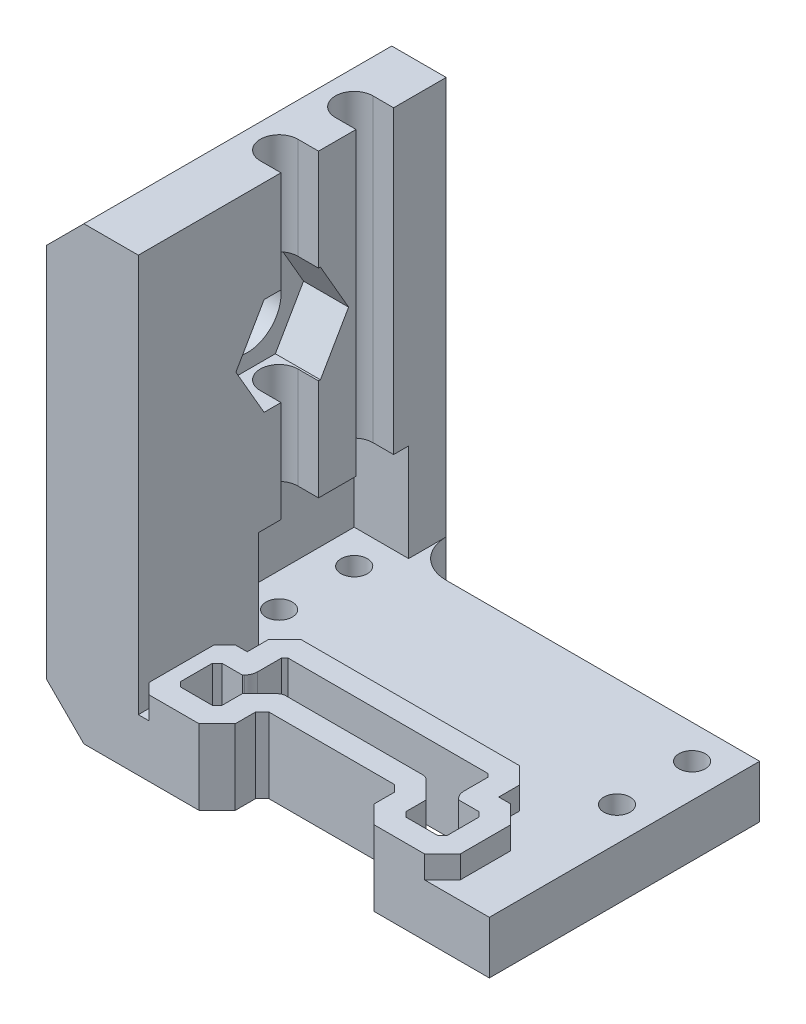
SolidWorks part; units mm, degrees
ref_plane "Front Plane" through (0, 0, 0) normal (0, 0, 1) x (1, 0, 0)
ref_plane "Top Plane" through (0, 0, 0) normal (0, 1, 0) x (1, 0, 0)
ref_plane "Right Plane" through (0, 0, 0) normal (1, 0, 0) x (0, 0, -1)
ref_plane "Plane1" through (0, 200, 0) normal (0, 1, 0) x (1, 0, 0)
sketch "Sketch1" plane through (0, 200, 0) normal (0, 1, 0) x (1, 0, 0)
  line L0 (0, -3.8557) -> (0.25, -4)
  line L1 (0.25, -4) -> (9.0787, -4)
  line L2 (10.1394, -4.4394) -> (12.5, -6.8)
  line L3 (12.5, -6.8) -> (12.5, -9.5)
  line L4 (12.5, -9.5) -> (13, -10)
  line L5 (13, -10) -> (17, -10)
  line L6 (17, -10) -> (17.5, -9.5)
  line L7 (17.5, -9.5) -> (17.5, -5.5)
  line L8 (17.5, -5.5) -> (17, -5)
  line L9 (17, -5) -> (14.3, -5)
  line L10 (14.3, -5) -> (14.0858, -4.7858)
  line L11 (13.5, -3.3716) -> (13.5, -0.3)
  line L12 (13.5, -0.3) -> (13.2, 0)
  line L13 (13.2, 0) -> (7.5, 0)
  line L14 (7.5, 0) -> (7.4, -0.1)
  line L15 (7.4, -0.1) -> (-7.4, -0.1)
  line L16 (-7.4, -0.1) -> (-7.5, 0)
  line L17 (-7.5, 0) -> (-13.2, 0)
  line L18 (-13.2, 0) -> (-13.5, -0.3)
  line L19 (-13.5, -0.3) -> (-13.5, -3.3716)
  line L20 (-14.0858, -4.7858) -> (-14.3, -5)
  line L21 (-14.3, -5) -> (-17, -5)
  line L22 (-17, -5) -> (-17.5, -5.5)
  line L23 (-17.5, -5.5) -> (-17.5, -9.5)
  line L24 (-17.5, -9.5) -> (-17, -10)
  line L25 (-17, -10) -> (-13, -10)
  line L26 (-13, -10) -> (-12.5, -9.5)
  line L27 (-12.5, -9.5) -> (-12.5, -6.8)
  line L28 (-12.5, -6.8) -> (-10.1394, -4.4394)
  line L29 (-9.0787, -4) -> (-0.25, -4)
  line L30 (-0.25, -4) -> (0, -3.8557)
  arc A0 (9.0787, -4) -> (10.1394, -4.4394) centre (9.0787, -5.5) cw
  arc A1 (14.0858, -4.7858) -> (13.5, -3.3716) centre (15.5, -3.3716) cw
  arc A2 (-13.5, -3.3716) -> (-14.0858, -4.7858) centre (-15.5, -3.3716) cw
  arc A3 (-10.1394, -4.4394) -> (-9.0787, -4) centre (-9.0787, -5.5) cw
extrude "Boss-Extrude1" add sketch "Sketch1" against normal blind 400
ref_plane "Plane2" through (0, 210, 0) normal (0, 1, 0) x (1, 0, 0)
sketch "Sketch2" plane through (0, 210, 0) normal (0, 1, 0) x (1, 0, 0)
  line L0 (-8.3538, -7.25) -> (8.3538, -7.25)
  line L1 (8.3538, -7.25) -> (9.25, -8.1462)
  line L2 (13.3036, 0.25) -> (-13.3036, 0.25)
  line L3 (-13.3036, 0.25) -> (-13.75, -0.1965)
  line L4 (-13.75, -0.1965) -> (-13.75, -3.3716)
  line L5 (-14.2626, -4.609) -> (-14.4036, -4.75)
  line L6 (-14.4036, -4.75) -> (-17.1036, -4.75)
  line L7 (-17.1036, -4.75) -> (-17.75, -5.3965)
  line L8 (-17.75, -5.3965) -> (-17.75, -9.6036)
  line L9 (-17.75, -9.6036) -> (-17.1036, -10.25)
  line L10 (-17.1036, -10.25) -> (-12.8965, -10.25)
  line L11 (-12.8965, -10.25) -> (-12.25, -9.6036)
  line L12 (-12.25, -9.6036) -> (-12.25, -6.9036)
  line L13 (-12.25, -6.9036) -> (-9.9626, -4.6162)
  line L14 (-9.0787, -4.25) -> (9.0787, -4.25)
  line L15 (9.9626, -4.6162) -> (12.25, -6.9036)
  line L16 (12.25, -6.9036) -> (12.25, -9.6036)
  line L17 (12.25, -9.6036) -> (12.8965, -10.25)
  line L18 (12.8965, -10.25) -> (17.1036, -10.25)
  line L19 (17.1036, -10.25) -> (17.75, -9.6036)
  line L20 (17.75, -9.6036) -> (17.75, -5.3965)
  line L21 (17.75, -5.3965) -> (17.1036, -4.75)
  line L22 (17.1036, -4.75) -> (14.4036, -4.75)
  line L23 (14.4036, -4.75) -> (14.2626, -4.609)
  line L24 (13.75, -3.3716) -> (13.75, -0.1965)
  line L25 (13.75, -0.1965) -> (13.3036, 0.25)
  line L26 (9.25, -8.1462) -> (9.25, -10.8462)
  line L27 (9.25, -10.8462) -> (11.6538, -13.25)
  line L28 (11.6538, -13.25) -> (18.3462, -13.25)
  line L29 (18.3462, -13.25) -> (20.75, -10.8462)
  line L30 (20.75, -10.8462) -> (20.75, -4.1538)
  line L31 (20.75, -4.1538) -> (18.3462, -1.75)
  line L32 (18.3462, -1.75) -> (16.75, -1.75)
  line L33 (16.75, -1.75) -> (16.75, -1.75)
  line L34 (16.75, -1.75) -> (16.75, 1.0462)
  line L35 (16.75, 1.0462) -> (14.5462, 3.25)
  line L36 (14.5462, 3.25) -> (-14.5462, 3.25)
  line L37 (-14.5462, 3.25) -> (-16.75, 1.0462)
  line L38 (-16.75, 1.0462) -> (-16.75, -1.75)
  line L39 (-16.75, -1.75) -> (-16.75, -1.75)
  line L40 (-16.75, -1.75) -> (-18.3462, -1.75)
  line L41 (-18.3462, -1.75) -> (-20.75, -4.1538)
  line L42 (-20.75, -4.1538) -> (-20.75, -10.8462)
  line L43 (-20.75, -10.8462) -> (-18.3462, -13.25)
  line L44 (-18.3462, -13.25) -> (-11.6538, -13.25)
  line L45 (-11.6538, -13.25) -> (-9.25, -10.8462)
  line L46 (-9.25, -10.8462) -> (-9.25, -8.1462)
  line L47 (-9.25, -8.1462) -> (-8.3538, -7.25)
  arc A0 (-14.2626, -4.609) -> (-13.75, -3.3716) centre (-15.5, -3.3716) ccw
  arc A1 (-9.0787, -4.25) -> (-9.9626, -4.6162) centre (-9.0787, -5.5) ccw
  arc A2 (9.9626, -4.6162) -> (9.0787, -4.25) centre (9.0787, -5.5) ccw
  arc A3 (13.75, -3.3716) -> (14.2626, -4.609) centre (15.5, -3.3716) ccw
  arc A4 (8.3538, -7.25) -> (8.3538, -7.25) centre (8.3538, -7.25) ccw
  arc A5 (16.75, -1.75) -> (16.75, -1.75) centre (16.75, -1.75) ccw
  arc A6 (-16.75, -1.75) -> (-16.75, -1.75) centre (-16.75, -1.75) ccw
  arc A7 (-8.3538, -7.25) -> (-8.3538, -7.25) centre (-8.3538, -7.25) ccw
  dimension "D1" = 3
extrude "Boss-Extrude2" add sketch "Sketch2" along normal blind 10 separate body
sketch "Sketch3" plane through (0, 200, 0) normal (0, 1, 0) x (1, 0, 0)
  line L0 (7.4, -0.1) -> (-7.4, -0.1) construction
  circle A0 centre (0, -0.1) radius 43.001
extrude "Cut-Extrude1" cut sketch "Sketch3" against normal blind 447.3602
sketch "Sketch4" plane through (0, 210, 0) normal (0, -1, 0) x (-1, 0, 0)
  line L0 (-13.3036, 0.25) -> (13.3036, 0.25) construction
  line L1 (27, 22.75) -> (-27, 22.75)
  line L2 (27, 22.75) -> (27, -13.25)
  line L3 (27, -13.25) -> (18.3462, -13.25)
  line L4 (-27, 22.75) -> (-27, -13.25)
  line L5 (-27, -13.25) -> (-18.3462, -13.25)
  line L25 (8.3538, -7.25) -> (9.25, -8.1462)
  line L26 (9.25, -8.1462) -> (9.25, -10.8462)
  line L27 (9.25, -10.8462) -> (11.6538, -13.25)
  line L28 (11.6538, -13.25) -> (18.3462, -13.25)
  line L29 (18.3462, -13.25) -> (20.75, -10.8462)
  line L30 (20.75, -10.8462) -> (20.75, -4.1538)
  line L31 (20.75, -4.1538) -> (18.3462, -1.75)
  line L32 (18.3462, -1.75) -> (16.75, -1.75)
  line L33 (16.75, -1.75) -> (16.75, 1.0462)
  line L34 (16.75, 1.0462) -> (14.5462, 3.25)
  line L35 (14.5462, 3.25) -> (-14.5462, 3.25)
  line L36 (-14.5462, 3.25) -> (-16.75, 1.0462)
  line L37 (-16.75, 1.0462) -> (-16.75, -1.75)
  line L38 (-16.75, -1.75) -> (-18.3462, -1.75)
  line L39 (-18.3462, -1.75) -> (-20.75, -4.1538)
  line L40 (-20.75, -4.1538) -> (-20.75, -10.8462)
  line L41 (-20.75, -10.8462) -> (-18.3462, -13.25)
  line L42 (-18.3462, -13.25) -> (-11.6538, -13.25)
  line L43 (-11.6538, -13.25) -> (-9.25, -10.8462)
  line L44 (-9.25, -10.8462) -> (-9.25, -8.1462)
  line L45 (-9.25, -8.1462) -> (-8.3538, -7.25)
  line L46 (-8.3538, -7.25) -> (8.3538, -7.25)
  line L47 (8.3538, -7.25) -> (9.25, -8.1462)
  line L48 (9.25, -8.1462) -> (9.25, -10.8462)
  line L49 (9.25, -10.8462) -> (11.6538, -13.25)
  line L50 (11.6538, -13.25) -> (18.3462, -13.25)
  line L51 (18.3462, -13.25) -> (20.75, -10.8462)
  line L52 (20.75, -10.8462) -> (20.75, -4.1538)
  line L53 (20.75, -4.1538) -> (18.3462, -1.75)
  line L54 (18.3462, -1.75) -> (16.75, -1.75)
  line L55 (16.75, -1.75) -> (16.75, 1.0462)
  line L56 (16.75, 1.0462) -> (14.5462, 3.25)
  line L57 (14.5462, 3.25) -> (-14.5462, 3.25)
  line L58 (-14.5462, 3.25) -> (-16.75, 1.0462)
  line L59 (-16.75, 1.0462) -> (-16.75, -1.75)
  line L60 (-16.75, -1.75) -> (-18.3462, -1.75)
  line L61 (-18.3462, -1.75) -> (-20.75, -4.1538)
  line L62 (-20.75, -4.1538) -> (-20.75, -10.8462)
  line L63 (-20.75, -10.8462) -> (-18.3462, -13.25)
  line L64 (-18.3462, -13.25) -> (-11.6538, -13.25)
  line L65 (-11.6538, -13.25) -> (-9.25, -10.8462)
  line L66 (-9.25, -10.8462) -> (-9.25, -8.1462)
  line L67 (-9.25, -8.1462) -> (-8.3538, -7.25)
  line L68 (-8.3538, -7.25) -> (8.3538, -7.25)
  point P8 (0, 22.75)
  point P29 (0, 0.25)
  dimension "D2" = 19.5
  dimension "D3" = 54
  dimension "D4" = 0
  dimension "D1" = 0
extrude "Boss-Extrude3" add sketch "Sketch4" against normal blind 7
sketch "Sketch5" plane through (0, 210, 0) normal (0, -1, 0) x (-1, 0, 0)
  line L0 (0, 22.75) -> (0, 9.6848) construction
  line L1 (27, 22.75) -> (-27, 22.75) construction
  line L2 (27, 22.75) -> (27, -13.25) construction
  circle A0 centre (22.5, 18.25) radius 1.75
  circle A1 centre (22.5, 8.25) radius 1.75
  circle A2 centre (-22.5, 8.25) radius 1.75
  circle A3 centre (-22.5, 18.25) radius 1.75
  dimension "D4" = 3.5
  dimension "D1" = 10
  dimension "D2" = 4.5
  dimension "D3" = 4.5
extrude "Cut-Extrude2" cut sketch "Sketch5" against normal blind 33
sketch "Sketch6" plane through (-27, 0, 0) normal (-1, 0, 0) x (0, 0, 1)
  line L1 (-22.75, 210) -> (13.25, 210)
  line L2 (-22.75, 210) -> (-22.75, 270)
  line L3 (-22.75, 270) -> (13.25, 270)
  line L4 (13.25, 210) -> (13.25, 270)
  dimension "D1" = 60
extrude "Boss-Extrude4" add sketch "Sketch6" along normal blind 5
sketch "Sketch7" plane through (0, 217, 0) normal (0, 1, 0) x (1, 0, 0)
  line L0 (-20.75, -10.8462) -> (-20.75, -4.1538) construction
  line L1 (-27, -13.25) -> (-19.75, -13.25)
  line L2 (-27, -13.25) -> (-27, 2.75)
  line L3 (-27, 2.75) -> (-19.75, 2.75)
  line L4 (-19.75, -13.25) -> (-19.75, 2.75)
  dimension "D1" = 1
  dimension "D2" = 16
extrude "Boss-Extrude5" add sketch "Sketch7" along normal up to surface (53 mm away) up to face at (-29.5, 270, -4.75)
sketch "Sketch8" plane through (0, 0, -22.75) normal (0, 0, -1) x (-1, 0, 0)
  line L0 (32, 210) -> (-27, 210) construction
  line L1 (32, 270) -> (19.75, 270)
  line L2 (32, 270) -> (32, 210)
  line L3 (32, 210) -> (19.75, 210)
  line L4 (19.75, 270) -> (19.75, 210)
  dimension "D1" = 0
extrude "Boss-Extrude6" add sketch "Sketch8" along normal blind 5
fillet "Fillet1" radius 5 1 edges at (-19.75, 213.5, -22.75)
sketch "Sketch10" plane through (-27, 0, 0) normal (1, 0, 0) x (0, 0, -1)
  line L0 (22.75, 270) -> (22.75, 217) construction
  line L1 (2.75, 270) -> (22.75, 270)
  line L2 (2.75, 270) -> (2.75, 230)
  line L3 (2.75, 230) -> (22.75, 230)
  line L4 (22.75, 270) -> (22.75, 230)
  dimension "D1" = 40
extrude "Boss-Extrude7" add sketch "Sketch10" along normal up to surface (7.25 mm away) up to face at (-19.75, 231, 6.375)
sketch "Sketch9" plane through (-19.75, 0, 0) normal (1, 0, 0) x (0, 0, -1)
  line L0 (-13.25, 250) -> (27.75, 250) construction
  line L1 (14.7555, 250) -> (11.0027, 256.5)
  line L2 (11.0027, 256.5) -> (3.4972, 256.5)
  line L3 (3.4972, 256.5) -> (-0.2556, 250)
  line L4 (-0.2556, 250) -> (3.4972, 243.5)
  line L5 (3.4972, 243.5) -> (11.0027, 243.5)
  line L6 (11.0027, 243.5) -> (14.7555, 250)
  line L8 (-13.25, 270) -> (-13.25, 217) construction
  line L9 (27.75, 270) -> (27.75, 217) construction
  line L10 (27.75, 270) -> (-13.25, 270) construction
  circle A0 centre (7.25, 250) radius 6.5 construction
  dimension "D1" = 13
  dimension "D2" = 20
extrude "Cut-Extrude3" cut sketch "Sketch9" against normal blind 6
sketch "Sketch11" plane through (0, 217, 0) normal (0, 1, 0) x (1, 0, 0)
  line L0 (-22.5, 20.75) -> (-17.8248, 20.75)
  line L1 (-17.8248, 20.75) -> (-17.8248, 15.75)
  line L2 (-17.8248, 15.75) -> (-22.5, 15.75)
  line L3 (-22.5, 10.75) -> (-17.8248, 10.75)
  line L4 (-17.8248, 10.75) -> (-17.8248, 5.75)
  line L5 (-17.8248, 5.75) -> (-22.5, 5.75)
  arc A0 (-22.5, 20.75) -> (-22.5, 15.75) centre (-22.5, 18.25) ccw
  arc A1 (-22.5, 10.75) -> (-22.5, 5.75) centre (-22.5, 8.25) ccw
  dimension "D1" = 5
  dimension "D2" = 5
extrude "Cut-Extrude4" cut sketch "Sketch11" along normal through all
sketch "Sketch12" plane through (-25.75, 0, 0) normal (1, 0, 0) x (0, 0, -1)
  line L0 (14.7555, 250) -> (-0.2556, 250) construction
  circle A0 centre (7.25, 250) radius 4.5
  dimension "D1" = 9
extrude "Cut-Extrude5" cut sketch "Sketch12" against normal blind 16
chamfer "Chamfer2" distance 5 angle 45 1 edges at (-32, 270, -7.25)
chamfer "Chamfer3" distance 5 angle 45 1 edges at (-32, 210, -7.25)
sketch "Sketch13" plane through (-32, 0, 0) normal (-1, 0, 0) x (0, 0, 1)
  circle A0 centre (-7.25, 250) radius 4.5
  circle A1 centre (-7.25, 250) radius 6.5
  dimension "D1" = 2
extrude "Boss-Extrude8" add sketch "Sketch13" along normal blind 1
fillet "Fillet2" radius 1 1 edges at (-32, 250, -13.75)
